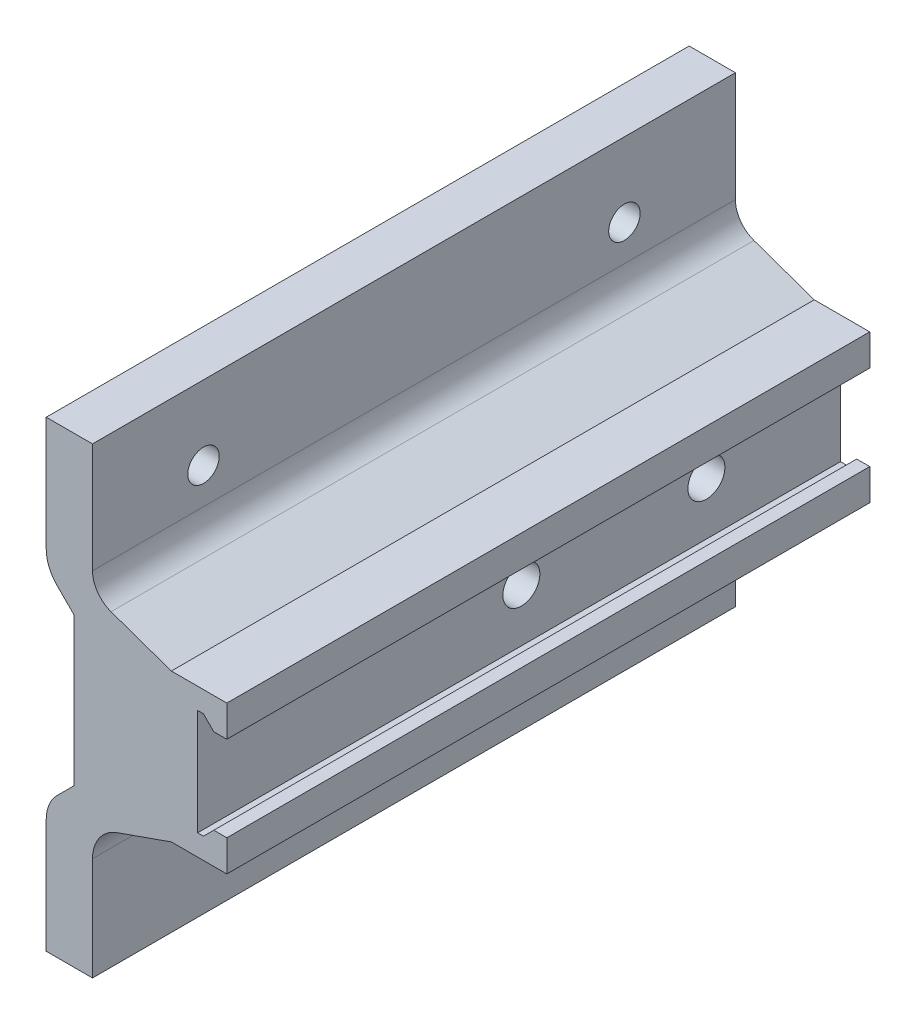
SolidWorks part; units mm, degrees
ref_plane "Front Plane" through (0, 0, 0) normal (0, 0, 1) x (1, 0, 0)
ref_plane "Top Plane" through (0, 0, 0) normal (0, 1, 0) x (1, 0, 0)
ref_plane "Right Plane" through (0, 0, 0) normal (1, 0, 0) x (0, 0, -1)
sketch "Sketch4" plane through (0, 0, 0) normal (0, 0, 1) x (1, 0, 0)
  line L1 (-4.3026, 10.3735) -> (-10.3026, 10.3735)
  line L2 (-6.8326, 8.1035) -> (-5.7126, 6.9835)
  line L3 (-7.4626, 8.1035) -> (-7.4626, -3.3565)
  line L4 (-6.8326, 8.1035) -> (-7.4626, 8.1035)
  line L5 (-13.1609, 2.3735) -> (1.8792, 2.3735) construction
  line L6 (-10.3026, 10.3735) -> (-10.3026, -5.6265)
  line L7 (-4.3026, 6.9835) -> (-4.3026, 10.3735)
  line L8 (-4.3026, -2.2365) -> (-4.3026, -5.6265)
  line L9 (-6.8326, -3.3565) -> (-7.4626, -3.3565)
  line L10 (-6.8326, -3.3565) -> (-5.7126, -2.2365)
  line L11 (-4.3026, -5.6265) -> (-10.3026, -5.6265)
  line L13 (-5.7126, 6.9835) -> (-4.3026, 6.9835)
  line L14 (-5.7126, -2.2365) -> (-4.3026, -2.2365)
  point P13 (-10.3026, 2.3735)
  point P15 (-7.4626, 2.3735)
  dimension "D1" = 1.12
  dimension "D3" = 1.12
  dimension "D4" = 0.63
  dimension "D5" = 5.73
  dimension "D6" = 2.53
  dimension "D7" = 16
  dimension "D8" = 1.12
extrude "Boss-Extrude2" add sketch "Sketch4" along normal blind 69.5
sketch "Sketch6" plane through (0, 0, 69.5) normal (0, 0, 1) x (1, 0, 0)
  line L0 (-7.4626, 2.3735) -> (-26.1204, 2.3735) construction
  line L1 (-7.4626, -3.3565) -> (-7.4626, 8.1035) construction
  line L2 (-18.8238, 27.3735) -> (-23.8238, 27.3735)
  line L3 (-23.8238, 27.3735) -> (-23.8238, 15.0303)
  line L4 (-10.3026, 10.3735) -> (-10.3026, -5.6265)
  line L5 (-10.3026, 10.3735) -> (-10.3026, -5.6265) construction
  line L6 (-18.8238, -22.6265) -> (-23.8238, -22.6265)
  line L7 (-18.8238, 27.3735) -> (-18.8238, 15.4978)
  line L8 (-16.82, 12.668) -> (-10.3026, 10.3735)
  line L9 (-16.1521, -7.6859) -> (-10.3026, -5.6265)
  line L10 (-18.8238, -22.6265) -> (-18.8238, -11.4589)
  line L11 (-22.6522, 12.2019) -> (-20.8238, 10.3735)
  line L12 (-20.8238, 10.3735) -> (-20.8238, -5.6265)
  line L13 (-20.8238, -5.6265) -> (-22.6522, -7.455)
  line L14 (-23.8238, -10.2834) -> (-23.8238, -22.6265)
  arc A1 (-16.82, 12.668) -> (-18.8238, 15.4978) centre (-15.8238, 15.4978) cw
  arc A2 (-18.8238, -11.4589) -> (-16.1521, -7.6859) centre (-14.8238, -11.4589) cw
  arc A3 (-22.6522, 12.2019) -> (-23.8238, 15.0303) centre (-19.8238, 15.0303) cw
  arc A4 (-23.8238, -10.2834) -> (-22.6522, -7.455) centre (-19.8238, -10.2834) cw
  point P16 (-10.3026, 2.3735)
  point P17 (-23.8238, 2.3735)
  point P23 (-18.8238, 13.3735)
  point P26 (-18.8238, -8.6265)
  point P31 (-23.8238, -8.6265)
  dimension "D1" = 14
  dimension "D6" = 3
  dimension "D7" = 4
  dimension "D8" = 4
  dimension "D9" = 4
  dimension "D2" = 50
  dimension "D3" = 5
  dimension "D4" = 3
  dimension "D5" = 16
extrude "Boss-Extrude3" add sketch "Sketch6" against normal up to surface (69.5 mm away) up to face at (-6.4859, 2.3735, 0)
sketch "Sketch7" plane through (-7.4626, 0, 0) normal (1, 0, 0) x (0, 0, -1)
  line L0 (-69.5, 2.3735) -> (0, 2.3735) construction
  line L1 (-69.5, -3.3565) -> (-69.5, 8.1035) construction
  line L2 (0, -3.3565) -> (0, 8.1035) construction
  circle A0 centre (-34.5, 2.3735) radius 2
  circle A1 centre (-14.5, 2.3735) radius 2
  dimension "D1" = 4
  dimension "D2" = 4
  dimension "D3" = 35
  dimension "D4" = 55
extrude "Cut-Extrude1" cut sketch "Sketch7" against normal through all and the other way through all
sketch "Sketch8" plane through (-23.8238, 0, 0) normal (-1, 0, 0) x (0, 0, 1)
  line L0 (0, 2.3735) -> (69.5, 2.3735) construction
  line L1 (0, 27.3735) -> (0, 15.0303) construction
  line L2 (69.5, 27.3735) -> (69.5, 15.0303) construction
  line L3 (0, 27.3735) -> (69.5, 27.3735) construction
  line L4 (0, 10.3735) -> (0, -5.6265) construction
  line L5 (69.5, 10.3735) -> (69.5, -5.6265) construction
  circle A0 centre (12, 19.3735) radius 1.7
  circle A1 centre (57.5, 19.3735) radius 1.7
  circle A4 centre (57.5, -14.6265) radius 1.7
  circle A5 centre (12, -14.6265) radius 1.7
  dimension "D1" = 3.4
  dimension "D2" = 3.4
  dimension "D3" = 12
  dimension "D4" = 12
  dimension "D5" = 8
  dimension "D6" = 8
extrude "Cut-Extrude2" cut sketch "Sketch8" against normal through all and the other way through all
